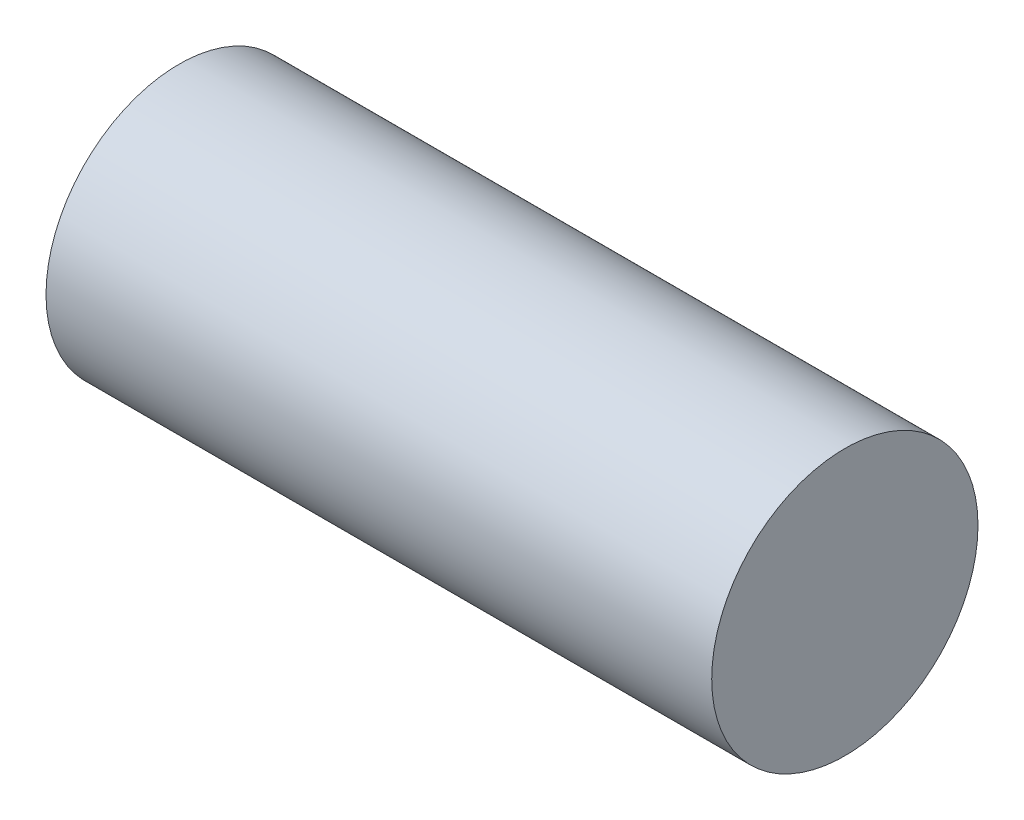
SolidWorks part; units mm, degrees
ref_plane "Front" through (0, 0, 0) normal (0, 0, 1) x (1, 0, 0)
ref_plane "Top" through (0, 0, 0) normal (0, 1, 0) x (1, 0, 0)
ref_plane "Right" through (0, 0, 0) normal (1, 0, 0) x (0, 0, -1)
sketch "Sketch1" plane through (0, 0, 0) normal (1, 0, 0) x (0, 0, -1)
  circle A0 centre (0, 0) radius 150
  dimension "D1" = 300
extrude "Boss-Extrude1" add sketch "Sketch1" along normal blind 750
